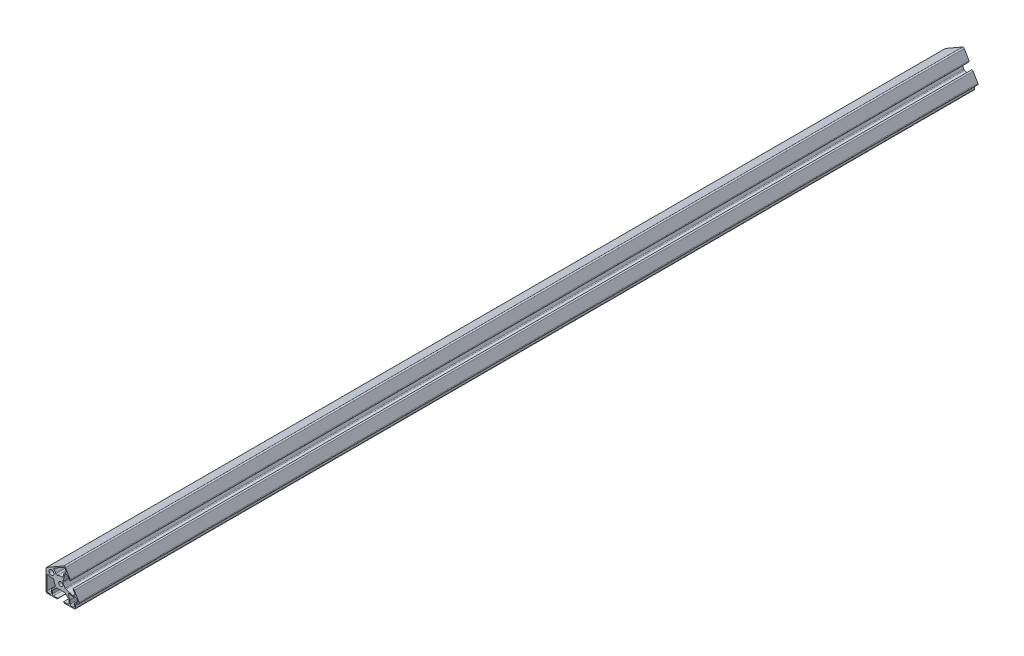
SolidWorks part; units mm, degrees
ref_plane "Front Plane" through (0, 0, 0) normal (0, 0, 1) x (1, 0, 0)
ref_plane "Top Plane" through (0, 0, 0) normal (0, 1, 0) x (1, 0, 0)
ref_plane "Right Plane" through (0, 0, 0) normal (1, 0, 0) x (0, 0, -1)
sketch "Sketch1" plane through (0, 0, 0) normal (0, 0, 1) x (1, 0, 0)
  line L1 (-4.8431, 22.7885) -> (-5.7091, 22.2885)
  line L3 (0, 0) -> (0, 4.8)
  line L4 (0, 4.8) -> (4.1569, 7.2)
  line L5 (4.1569, 7.2) -> (-1.8431, 17.5923)
  line L6 (-8.9591, 27.9176) -> (-11.2091, 31.8147)
  line L7 (0.5409, 11.4631) -> (-2.2091, 9.8754)
  line L8 (-10.8431, 33.1808) -> (-30, 22.1205)
  line L9 (-4.8431, 22.7885) -> (-10.8431, 33.1808)
  line L10 (-5.7091, 22.2885) -> (-8.4591, 27.0516)
  line L11 (-1.8431, 17.5923) -> (-2.7091, 17.0923)
  line L12 (-2.7091, 17.0923) -> (0.0409, 12.3292)
  line L13 (-1, 1) -> (-1, 5.3774)
  line L14 (2.7909, 7.566) -> (-1, 5.3774)
  line L15 (-18, 1) -> (-23.5, 1)
  line L16 (-12, 0) -> (-12, 1) construction
  line L17 (-12, 0) -> (-12, 1)
  line L18 (-12, 1) -> (-6.5, 1)
  line L19 (-18, 1) -> (-18, 0)
  line L20 (-29, 1) -> (-29, 19.4568)
  line L21 (-23.1534, 24.9187) -> (-11.2091, 31.8147)
  line L22 (-8.4591, 27.0516) -> (-10.8504, 25.671)
  line L23 (-18, 0) -> (-30, 0)
  line L25 (-12, 0) -> (0, 0)
  line L26 (-23.5, 5.3) -> (-19.2, 9.6)
  line L28 (-25.0413, 18.0552) -> (-25.0413, 18.0593)
  line L31 (-25.0362, 18.0582) -> (-25.0413, 18.0552) construction
  line L32 (-30, 22.1205) -> (-30, 0)
  line L33 (-6.5, 5.4) -> (-10.7, 9.6)
  line L34 (-5.5, 1) -> (-5.5, 5.7523)
  line L35 (-6.5, 1) -> (-6.5, 5.4)
  line L36 (0.0409, 12.3292) -> (-2.3504, 10.9486)
  line L38 (-10.8504, 25.671) -> (-12.9875, 17.6951)
  line L39 (-5.5, 1) -> (-1, 1)
  line L40 (0.5409, 11.4631) -> (2.7909, 7.566)
  line L41 (-12.9875, 17.6951) -> (-10.3263, 13.0857)
  line L42 (-11.7091, 26.3299) -> (-12.9926, 21.5399)
  line L43 (-10.8431, 33.1808) -> (6.1668, 43.0014)
  line L44 (-24.5, 1) -> (-24.5, 5.9728)
  line L45 (-23.5, 1) -> (-23.5, 5.3)
  line L46 (-20.8728, 9.6) -> (-24.5, 5.9728)
  line L47 (-24.5, 1) -> (-29, 1)
  line L49 (6.1668, 43.0014) -> (13.6668, 30.011)
  line L52 (-5.5, 5.7523) -> (-7.2082, 8.711)
  line L53 (-2.2091, 9.8754) -> (-4.8722, 10.589)
  line L54 (-19.2, 9.6) -> (-10.7, 9.6)
  line L56 (-8.9591, 27.9176) -> (-11.7091, 26.3299)
  line L57 (-8.9591, 27.9176) -> (-11.7091, 26.3299)
  line L61 (-2.3504, 10.9486) -> (-10.3263, 13.0857)
  line L62 (-20.8728, 9.6) -> (-20.0358, 10.3696)
  line L63 (0.5409, 11.4631) -> (-2.2091, 9.8754)
  line L75 (-6.4379, 9.6) -> (-6.439, 9.6018)
  circle A6 centre (-24.5, 20.5) radius 2.5
  arc A7 (-29, 19.4568) -> (-22.8919, 16.1696) centre (-24.5, 20.5) ccw
  circle A13 centre (-15, 15) radius 2.0923
  arc A15 (-4.8722, 10.589) -> (-7.2082, 8.711) centre (-6, 9.6) ccw
  arc A17 (-29, 19.4568) -> (-21.5614, 16.9359) centre (-24.5, 20.5) ccw
  arc A18 (-21.5614, 16.9359) -> (-20.0358, 10.3696) centre (-15, 15) ccw
  arc A19 (-19.9459, 19.7263) -> (-23.1534, 24.9187) centre (-24.5, 20.5) ccw
  arc A20 (-12.9926, 21.5399) -> (-19.9459, 19.7263) centre (-15, 15) ccw
  dimension "D4" = 12
  dimension "D21" = 5
  dimension "D13" = 9.6
  dimension "D14" = 1
  dimension "D18" = 4.5
  dimension "D6" = 4.5
  dimension "D35" = 4.1846
  dimension "D8" = 3
  dimension "D25" = 5.5
  dimension "D3" = 1
  dimension "D5" = 1
  dimension "D7" = 9.6
  dimension "D9" = 4.5
  dimension "D10" = 12
  dimension "D11" = 30
  dimension "D12" = 12
  dimension "D15" = 0
  dimension "D16" = 6
  dimension "D17" = 1
  dimension "D19" = 1
  dimension "D20" = 6.5
  dimension "D22" = 5.5
  dimension "D23" = 9.6
  dimension "D24" = 6.5
  dimension "D26" = 15
  dimension "D27" = 8.6
  dimension "D28" = 15
  dimension "D29" = 5.5
  dimension "D30" = 0
  dimension "D31" = 9.6
  dimension "D32" = 9.6
  dimension "D34" = 45
extrude "Boss-Extrude1" add sketch "Sketch1" along normal blind 913.638
fillet "Fillet1" radius 1.27 9 edges at (4.1569, 7.2, 456.819) (-11.2091, 31.8147, 456.819) (-30, 22.1205, 456.819) (-30, 0, 456.819) (0, 0, 456.819) (-19.2, 9.6, 456.819) (-10.7, 9.6, 456.819) (-2.2091, 9.8754, 456.819) (-11.7091, 26.3299, 456.819)
fillet "Fillet2" radius 1.27 3 edges at (-6.5, 5.4, 456.819) (-20.0358, 10.3696, 456.819) (-24.5, 5.9728, 456.819)
fillet "Fillet3" radius 1.27 3 edges at (-23.5, 5.3, 456.819) (-10.8504, 25.671, 456.819) (-12.9875, 17.6951, 456.819)
fillet "Fillet4" radius 1.27 2 edges at (-10.3263, 13.0857, 456.819) (-2.3504, 10.9486, 456.819)
fillet "Fillet5" radius 1.27 4 edges at (2.7909, 7.566, 456.819) (-1, 5.3774, 456.819) (-4.8722, 10.589, 456.819)
fillet "Fillet6" radius 1.27 7 edges at (-5.5, 5.7523, 456.819) (-5.5, 1, 456.819) (-29, 1, 456.819) (-24.5, 1, 456.819) (-6.5, 1, 456.819) (-1, 1, 456.819) (-23.5, 1, 456.819)
fillet "Fillet7" radius 1.27 6 edges at (-19.9459, 19.7263, 456.819) (-21.5614, 16.9359, 456.819) (-8.4591, 27.0516, 456.819) (-12.9926, 21.5399, 456.819) (-8.9591, 27.9176, 456.819) (0.0409, 12.3292, 456.819)
fillet "Fillet8" radius 1.27 2 edges at (-23.1534, 24.9187, 456.819) (0, 4.8, 456.819)
fillet "Fillet9" radius 1.27 1 edges at (-29, 19.4568, 456.819)
fillet "Fillet10" radius 1.27 2 edges at (-12, 0, 456.819) (-18, 0, 456.819)
fillet "Fillet11" radius 1.27 2 edges at (-4.8431, 22.7885, 456.819) (-1.8431, 17.5923, 456.819)
fillet "Fillet12" radius 1.27 1 edges at (-10.8431, 33.1808, 456.819)
